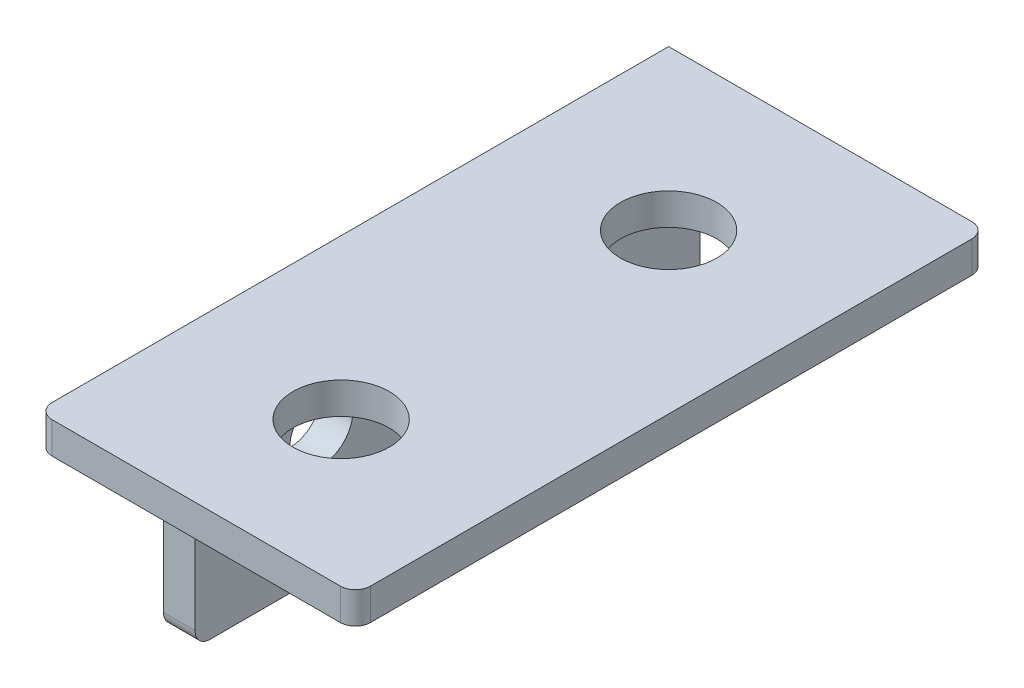
SolidWorks part; units mm, degrees
material "ABS"
ref_plane "Front Plane" through (0, 0, 0) normal (0, 0, 1) x (1, 0, 0)
ref_plane "Top Plane" through (0, 0, 0) normal (0, 1, 0) x (1, 0, 0)
ref_plane "Right Plane" through (0, 0, 0) normal (1, 0, 0) x (0, 0, -1)
sketch "Sketch2" plane through (0, 0, 0) normal (1, 0, 0) x (0, 0, -1)
  line L1 (-25.4, -12.7) -> (25.4, -12.7)
  line L2 (-25.4, -12.7) -> (-25.4, 12.7)
  line L3 (-25.4, 12.7) -> (25.4, 12.7)
  line L4 (25.4, -12.7) -> (25.4, 12.7)
  line L5 (-25.4, -12.7) -> (25.4, 12.7) construction
  line L6 (-25.4, 12.7) -> (25.4, -12.7) construction
  point P0 (0, 0)
  dimension "D1" = 25.4
  dimension "D2" = 50.8
extrude "Boss-Extrude1" add sketch "Sketch2" along normal blind 3.175
sketch "Sketch4" plane through (0, 12.7, 0) normal (0, 1, 0) x (1, 0, 0)
  line L1 (0, 25.4) -> (32, 25.4)
  line L2 (0, 25.4) -> (0, -38.1)
  line L3 (0, -38.1) -> (32, -38.1)
  line L4 (32, 25.4) -> (32, -38.1)
  dimension "D1" = 63.5
  dimension "D2" = 32
extrude "Boss-Extrude2" add sketch "Sketch4" against normal blind 3.175
sketch "Sketch6" plane through (0, 0, 0) normal (-1, 0, 0) x (0, 0, 1)
  line L0 (12.7, 0) -> (-12.7, 0) construction
  circle A0 centre (-12.7, 0) radius 3.175
  circle A1 centre (12.7, 0) radius 3.175
  point P4 (0, 0)
extrude "Cut-Extrude2" cut sketch "Sketch6" against normal blind 3.175
sketch "Sketch7" plane through (0, 0, 0) normal (0, 0, 1) x (1, 0, 0)
  line L2 (3.175, -12.7) -> (25.4, 9.525)
  line L3 (0, 9.525) -> (32, 9.525) construction
  line L8 (3.175, -12.7) -> (3.175, 9.525)
  line L9 (25.4, 9.525) -> (3.175, 9.525)
extrude "Boss-Extrude3" add sketch "Sketch7" along normal mid plane 3.175
sketch "Sketch8" plane through (0, 12.7, 0) normal (0, 1, 0) x (1, 0, 0)
  line L1 (16, -38.0862) -> (16, -23.5362) construction
  circle A3 centre (16, 9.4) radius 16 construction
  circle A4 centre (16, 9.4) radius 4.85
  circle A5 centre (16, -23.5362) radius 4.85
  circle A6 centre (16, -23.5362) radius 6.35 construction
extrude "Cut-Extrude3" cut sketch "Sketch8" against normal blind 10
fillet "Fillet3" radius 1.5 13 edges at (3.175, -1.5875, -1.5875) (14.2875, 9.525, -1.5875) (25.4, 9.525, 0) (3.175, -1.5875, 1.5875) (14.2875, 9.525, 1.5875) (3.175, 9.525, 13.4937) (3.175, 9.525, -13.4937) (1.5875, -12.7, 25.4) (1.5875, -12.7, -25.4) (32, 11.1125, 38.1) (32, 11.1125, -25.4) (1.5875, 9.525, 25.4) (0, 11.1125, 38.1)
